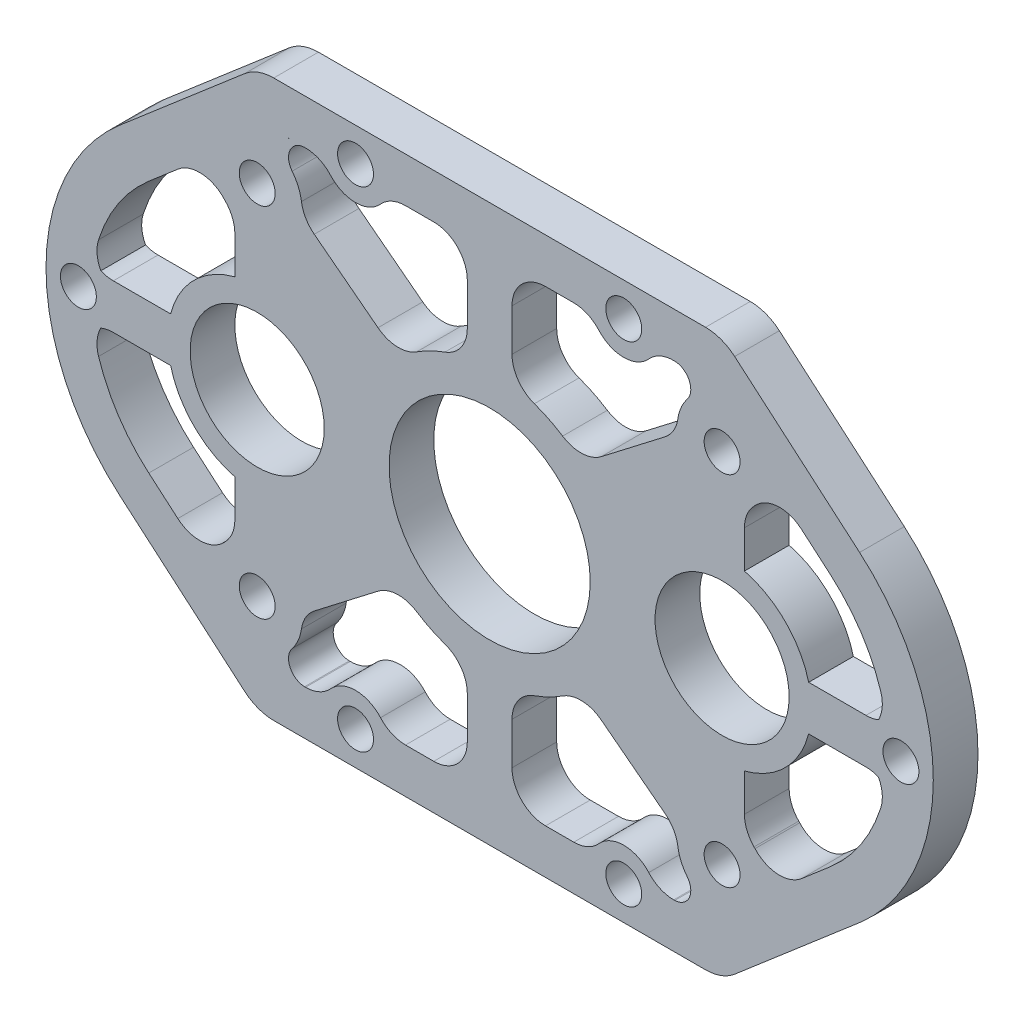
SolidWorks part; units mm, degrees
material "6061-T6 (SS)"
ref_plane "Front Plane" through (0, 0, 0) normal (0, 0, 1) x (1, 0, 0)
ref_plane "Top Plane" through (0, 0, 0) normal (0, 1, 0) x (1, 0, 0)
ref_plane "Right Plane" through (0, 0, 0) normal (1, 0, 0) x (0, 0, -1)
sketch "Sketch1" plane through (0, 0, 0) normal (0, 0, 1) x (1, 0, 0)
  line L0 (127, 25.4) -> (127, 0) construction
  line L1 (0, 0) -> (254, 0)
  line L2 (0, 0) -> (0, 25.4)
  line L3 (0, 25.4) -> (254, 25.4)
  line L4 (254, 0) -> (254, 25.4)
  line L18 (110.6338, 19.05) -> (106.9677, 12.7)
  line L19 (106.9677, 12.7) -> (110.6338, 6.35)
  line L20 (110.6338, 6.35) -> (117.9662, 6.35)
  line L21 (117.9662, 6.35) -> (121.6323, 12.7)
  line L22 (121.6323, 12.7) -> (117.9662, 19.05)
  line L23 (117.9662, 19.05) -> (110.6338, 19.05)
  circle A0 centre (81.28, 12.7) radius 30 construction
  circle A1 centre (147.32, 12.7) radius 30 construction
  circle A2 centre (81.28, 12.7) radius 7.62 construction
  circle A3 centre (147.32, 12.7) radius 8.636
  circle A4 centre (81.28, 12.7) radius 8.636
  circle A5 centre (147.32, 12.7) radius 7.62 construction
  circle A6 centre (114.3, 12.7) radius 25.4 construction
  circle A7 centre (114.3, 12.7) radius 26.67
  circle A8 centre (114.3, 12.7) radius 22.2377 construction
  circle A11 centre (114.3, 12.7) radius 6.35 construction
  point P46 (0, 12.7)
  dimension "D4" = 17.272
  dimension "D9" = 53.34
  dimension "D13" = 12.7
  dimension "D1" = 25.4
  dimension "D2" = 254
  dimension "D10" = 12.7
  dimension "D12" = 12.7
sketch "Sketch3" plane through (0, 0, 0) normal (0, 0, 1) x (1, 0, 0)
  line L0 (81.28, 42.7) -> (147.32, 42.7) construction
  line L5 (81.28, 12.7) -> (114.3, 12.7) construction
  line L6 (114.3, 12.7) -> (147.32, 12.7) construction
  line L9 (114.3, 42.7) -> (114.3, -17.3) construction
  line L10 (61.7477, 35.4704) -> (81.28, 52.225)
  line L25 (81.28, 52.225) -> (147.32, 52.225)
  line L26 (147.32, 52.225) -> (166.8523, 35.4704)
  line L27 (110.6338, 19.05) -> (106.9677, 12.7)
  line L28 (106.9677, 12.7) -> (110.6338, 6.35)
  line L29 (110.6338, 6.35) -> (117.9662, 6.35)
  line L30 (117.9662, 6.35) -> (121.6323, 12.7)
  line L31 (121.6323, 12.7) -> (117.9662, 19.05)
  line L32 (117.9662, 19.05) -> (110.6338, 19.05)
  line L33 (110.565, 18.9308) -> (106.9677, 12.7)
  line L34 (106.9677, 12.7) -> (110.6338, 6.35)
  line L35 (110.6338, 6.35) -> (117.9662, 6.35)
  line L36 (117.9662, 6.35) -> (121.6323, 12.7)
  line L37 (121.6323, 12.7) -> (117.9662, 19.05)
  line L38 (117.9662, 19.05) -> (110.6338, 19.05)
  line L39 (96.3395, 30.6605) -> (132.2605, -5.2605) construction
  line L40 (99.2405, 30.6605) -> (81.28, 12.7) construction
  line L41 (95.25, 47.4625) -> (133.35, 47.4625) construction
  line L42 (81.28, -17.3) -> (147.32, -17.3) construction
  line L43 (95.25, -22.0625) -> (133.35, -22.0625) construction
  line L44 (147.32, -26.825) -> (166.8523, -10.0704)
  line L45 (81.28, -26.825) -> (147.32, -26.825)
  line L46 (61.7477, -10.0704) -> (81.28, -26.825)
  line L47 (81.28, 12.7) -> (81.28, -12.7) construction
  line L48 (81.28, 12.7) -> (81.28, -12.7) construction
  line L49 (81.28, 12.7) -> (55.88, 12.7) construction
  circle A2 centre (81.28, 12.7) radius 30 construction
  circle A9 centre (114.3, 12.7) radius 26.67
  circle A10 centre (114.3, 12.7) radius 26.67 construction
  circle A11 centre (81.28, 12.7) radius 8.636
  circle A12 centre (81.28, 12.7) radius 8.636 construction
  circle A13 centre (147.32, 12.7) radius 8.636
  circle A16 centre (147.32, 12.7) radius 8.636 construction
  circle A17 centre (95.25, 47.4625) radius 2.5527
  circle A19 centre (114.3, 12.7) radius 25.4 construction
  circle A20 centre (114.3, 12.7) radius 22.2377 construction
  circle A22 centre (114.3, 12.7) radius 25.4 construction
  circle A23 centre (114.3, 12.7) radius 22.2377 construction
  arc A24 (108.3271, 25.6791) -> (108.3271, -0.2791) centre (81.28, 12.7) ccw
  circle A25 centre (114.3, 12.7) radius 14.2875
  circle A26 centre (81.28, 12.7) radius 9.525
  circle A27 centre (147.32, 12.7) radius 9.525
  circle A37 centre (133.35, 47.4625) radius 2.5527
  circle A38 centre (133.35, -22.0625) radius 2.5527
  circle A39 centre (95.25, -22.0625) radius 2.5527
  circle A40 centre (81.28, -12.7) radius 2.5527
  circle A41 centre (55.88, 12.7) radius 2.5527
  circle A42 centre (81.28, 38.1) radius 2.5527
  circle A43 centre (147.32, -12.7) radius 2.5527
  circle A44 centre (172.72, 12.7) radius 2.5527
  circle A45 centre (147.32, 38.1) radius 2.5527
  arc A47 (120.2729, -0.2791) -> (120.2729, 25.6791) centre (147.32, 12.7) ccw
  point P2 (114.3, 42.7)
  point P41 (114.3, 52.225)
  point P59 (114.3, 47.4625)
  point P69 (114.3, 12.7)
  point P78 (81.28, 12.7)
  point P84 (114.3, -22.0625)
  dimension "D3" = 45
  dimension "D4" = 9.525
  dimension "D2" = 45
  dimension "D8" = 25.4
  dimension "D14" = 28.575
  dimension "D15" = 19.05
  dimension "D16" = 3
  dimension "D5" = 5.1054
  dimension "D12" = 5.1054
  dimension "D7" = 4.7625
  dimension "D17" = 90
  dimension "2" = 50.8
  dimension "D6" = 19.05
  dimension "D9" = 0
  dimension "D10" = 0
  dimension "D11" = 0
  dimension "D13" = 0
extrude "Boss-Extrude1" add sketch "Sketch3" along normal blind 6.35 contours A24 A10 L26 L25 L10 A37 A17 | A24 L46 L45 L44 A10 A38 A39 | A10 A24 A12 A40 A42 | A23 A24 A25 | A23 A22 A12 | A22 A24 A10 A12 | A22 A12 A10 A24 | A24 A22 A23 | A24 A10 A22 | A22 A24 A23 | A25 A24 A23 | A25 A23 A24 | A24 A23 A22 | A24 A22 A10 | A23 A24 A22 | A23 A45 A25 A44 | A22 A45 A23 A44 A16 | A23 A45 A22 | A22 A45 A16 A10 | A10 A16 A43 | A22 A44 A23 | A22 A44 A10 A16 | A10 A26 A12 | A22 A12 A10 | A12 A22 | A10 A27 A16 | A16 A22 | A22 A16 A10 region at (81.1746, 41.9228, 0) region at (114.3, 45.5045, 0) region at (114.3, -20.1045, 0) region at (97.63, 12.7, 0) region at (114.3, 33.2042, 0) region at (114.3, -7.8042, 0) region at (147.4254, 41.9228, 0) region at (130.97, 12.7, 0)
fillet "Fillet2" radius 6.35 4 edges at (147.32, -26.825, 3.175) (81.28, -26.825, 3.175) (147.32, 52.225, 3.175) (81.28, 52.225, 3.175)
sketch "Sketch9" plane through (0, 0, 6.35) normal (0, 0, 1) x (1, 0, 0)
  line L0 (144.9696, -20.475) -> (162.7179, -5.2507)
  line L1 (162.7179, 30.6507) -> (144.9696, 45.875)
  line L2 (144.9696, 45.875) -> (83.6304, 45.875)
  line L3 (83.6304, 45.875) -> (65.8821, 30.6507)
  line L4 (65.8821, -5.2507) -> (83.6304, -20.475)
  line L5 (83.6304, -20.475) -> (144.9696, -20.475)
  line L6 (149.104, -25.2947) -> (166.8523, -10.0704)
  line L7 (166.8523, 35.4704) -> (149.104, 50.6947)
  line L8 (144.9696, 52.225) -> (83.6304, 52.225)
  line L9 (79.496, 50.6947) -> (61.7477, 35.4704)
  line L10 (61.7477, -10.0704) -> (79.496, -25.2947)
  line L11 (83.6304, -26.825) -> (144.9696, -26.825)
  line L12 (149.104, -25.2947) -> (166.8523, -10.0704)
  line L13 (166.8523, 35.4704) -> (149.104, 50.6947)
  line L14 (144.9696, 52.225) -> (83.6304, 52.225)
  line L15 (79.496, 50.6947) -> (61.7477, 35.4704)
  line L16 (61.7477, -10.0704) -> (79.496, -25.2947)
  line L17 (83.6304, -26.825) -> (144.9696, -26.825)
  line L18 (81.28, 38.1) -> (81.28, 12.7) construction
  line L19 (81.28, 12.7) -> (81.28, -12.7) construction
  line L20 (147.32, -12.7) -> (147.32, 12.7) construction
  line L21 (147.32, 12.7) -> (147.32, 38.1) construction
  line L22 (81.28, 12.7) -> (114.3, 12.7) construction
  line L23 (114.3, 12.7) -> (147.32, 12.7) construction
  line L24 (147.32, 12.7) -> (114.3, 12.7) construction
  line L25 (114.3, 12.7) -> (147.32, -12.7) construction
  line L26 (81.28, -12.7) -> (114.3, 12.7) construction
  line L27 (114.3, 12.7) -> (81.28, 38.1) construction
  line L28 (114.3, 12.7) -> (147.32, 38.1) construction
  line L29 (114.3, 12.7) -> (114.3, 45.875) construction
  line L30 (114.3, 12.7) -> (114.3, -20.475) construction
  line L31 (116.2358, 15.2166) -> (83.2158, 40.6166)
  line L32 (112.3642, 10.1834) -> (145.3842, -15.2166)
  line L33 (116.2358, 10.1834) -> (149.2558, 35.5834)
  line L34 (112.3642, 10.1834) -> (79.3442, 35.5834)
  line L35 (116.2358, 15.2166) -> (149.2558, -10.1834)
  line L36 (112.3642, 15.2166) -> (145.3842, 40.6166)
  line L37 (81.28, 12.7) -> (55.88, 12.7) construction
  line L38 (147.32, 12.7) -> (172.72, 12.7) construction
  line L39 (81.28, 9.525) -> (55.88, 9.525)
  line L40 (81.28, 9.525) -> (114.3, 9.525)
  line L41 (114.3, 9.525) -> (147.32, 9.525)
  line L42 (147.32, 9.525) -> (172.72, 9.525)
  line L43 (81.28, 15.875) -> (55.88, 15.875)
  line L44 (81.28, 15.875) -> (114.3, 15.875)
  line L45 (114.3, 15.875) -> (147.32, 15.875)
  line L46 (147.32, 15.875) -> (172.72, 15.875)
  line L47 (83.2158, -15.2166) -> (116.2358, 10.1834)
  line L48 (79.3442, -10.1834) -> (112.3642, 15.2166)
  line L49 (111.125, 12.7) -> (111.125, -20.475)
  line L50 (117.475, 12.7) -> (117.475, -20.475)
  line L51 (117.475, 12.7) -> (117.475, 45.875)
  line L52 (111.125, 12.7) -> (111.125, 45.875)
  line L53 (78.105, 38.1) -> (78.105, 12.7)
  line L54 (78.105, 12.7) -> (78.105, -12.7)
  line L55 (150.495, -12.7) -> (150.495, 12.7)
  line L56 (150.495, 12.7) -> (150.495, 38.1)
  line L57 (84.455, 38.1) -> (84.455, 12.7)
  line L58 (84.455, 12.7) -> (84.455, -12.7)
  line L59 (144.145, -12.7) -> (144.145, 12.7)
  line L60 (144.145, 12.7) -> (144.145, 38.1)
  circle A0 centre (55.88, 12.7) radius 4.6
  circle A1 centre (95.25, 47.4625) radius 4.7625
  arc A2 (166.8523, -10.0704) -> (166.8523, 35.4704) centre (147.32, 12.7) ccw
  arc A3 (61.7477, 35.4704) -> (61.7477, -10.0704) centre (81.28, 12.7) ccw
  arc A4 (166.8523, -10.0704) -> (166.8523, 35.4704) centre (147.32, 12.7) ccw
  arc A5 (61.7477, 35.4704) -> (61.7477, -10.0704) centre (81.28, 12.7) ccw
  circle A6 centre (133.35, 47.4625) radius 4.7625
  circle A7 centre (172.72, 12.7) radius 4.6
  circle A8 centre (133.35, -22.0625) radius 4.7625
  circle A9 centre (95.25, -22.0625) radius 4.7625
  circle A10 centre (81.28, 12.7) radius 9.525
  circle A11 centre (81.28, -12.7) radius 6.35
  circle A12 centre (81.28, 38.1) radius 6.35
  circle A13 centre (147.32, 38.1) radius 6.35
  circle A14 centre (147.32, 12.7) radius 9.525
  circle A15 centre (147.32, -12.7) radius 6.35
  arc A16 (144.9696, -26.825) -> (149.104, -25.2947) centre (144.9696, -20.475) ccw
  arc A17 (144.9696, -26.825) -> (149.104, -25.2947) centre (144.9696, -20.475) ccw
  arc A18 (149.104, 50.6947) -> (144.9696, 52.225) centre (144.9696, 45.875) ccw
  arc A19 (149.104, 50.6947) -> (144.9696, 52.225) centre (144.9696, 45.875) ccw
  arc A20 (83.6304, 52.225) -> (79.496, 50.6947) centre (83.6304, 45.875) ccw
  arc A21 (83.6304, 52.225) -> (79.496, 50.6947) centre (83.6304, 45.875) ccw
  arc A22 (79.496, -25.2947) -> (83.6304, -26.825) centre (83.6304, -20.475) ccw
  arc A23 (79.496, -25.2947) -> (83.6304, -26.825) centre (83.6304, -20.475) ccw
  arc A24 (162.7179, -5.2507) -> (162.7179, 30.6507) centre (147.32, 12.7) ccw
  arc A25 (144.9696, 45.875) -> (144.9696, 45.875) centre (144.9696, 45.875) ccw
  arc A26 (83.6304, 45.875) -> (83.6304, 45.875) centre (83.6304, 45.875) ccw
  arc A27 (65.8821, 30.6507) -> (65.8821, -5.2507) centre (81.28, 12.7) ccw
  arc A28 (83.6304, -20.475) -> (83.6304, -20.475) centre (83.6304, -20.475) ccw
  arc A29 (144.9696, -20.475) -> (144.9696, -20.475) centre (144.9696, -20.475) ccw
  circle A30 centre (114.3, 12.7) radius 19.05
  circle A32 centre (81.28, 12.7) radius 12.7
  circle A33 centre (147.32, 12.7) radius 12.7
  dimension "D2" = 19.05
  dimension "D3" = 12.7
  dimension "D4" = 38.1
  dimension "D18" = 25.4
  dimension "D17" = 6.35
  dimension "D1" = 0
  dimension "D5" = 3.175
  dimension "D6" = 3.175
  dimension "D7" = 3.175
  dimension "D8" = 3.175
  dimension "D9" = 3.175
  dimension "D10" = 3.175
  dimension "D11" = 3.175
  dimension "D12" = 3.175
  dimension "D13" = 3.175
  dimension "D14" = 3.175
  dimension "D15" = 3.175
  dimension "D16" = 3.175
extrude "Cut-Extrude2" cut sketch "Sketch9" against normal blind 6.35 contours A32 L53 A12 L3 A27 A0 L43 | A32 L39 A0 A27 L4 A11 L54 | A30 L52 L2 A1 L3 A12 L31 | A30 L36 A13 L1 L2 A6 L51 | A33 L46 A7 A24 L1 A13 L56 | A33 L55 A15 L0 A24 A7 L42 | A30 L50 L5 A8 L0 A15 L32 | A30 L47 A11 L4 L5 A9 L49 region at (128.7733, -12.6609, 6.35) region at (159.8487, -0.042, 6.35) region at (99.8267, -12.6609, 6.35) region at (159.8487, 25.442, 6.35) region at (68.7513, -0.042, 6.35) region at (128.7733, 38.0609, 6.35) region at (68.7513, 25.442, 6.35) region at (99.8267, 38.0609, 6.35)
fillet "Fillet3" radius 4.7625 48 edges at (117.475, 45.875, 3.175) (128.8599, 45.875, 3.175) (137.8401, 45.875, 3.175) (144.9696, 45.875, 3.175) (146.6698, 44.4166, 3.175) (141.0253, 37.2636, 3.175) (127.2525, 26.6691, 3.175) (117.475, 31.4836, 3.175) (101.3475, 26.6691, 3.175) (81.9302, 44.4166, 3.175) (83.6304, 45.875, 3.175) (90.7599, 45.875, 3.175) (99.7401, 45.875, 3.175) (111.125, 45.875, 3.175) (111.125, 31.4836, 3.175) (87.5747, 37.2636, 3.175) (111.125, -6.0836, 3.175) (111.125, -20.475, 3.175) (99.7401, -20.475, 3.175) (90.7599, -20.475, 3.175) (81.9302, -19.0166, 3.175) (87.5747, -11.8636, 3.175) (101.3475, -1.2691, 3.175) (83.6304, -20.475, 3.175) (127.2525, -1.2691, 3.175) (141.0253, -11.8636, 3.175) (146.6698, -19.0166, 3.175) (144.9696, -20.475, 3.175) (137.8401, -20.475, 3.175) (128.8599, -20.475, 3.175) (117.475, -6.0836, 3.175) (117.475, -20.475, 3.175) (169.3914, 15.875, 3.175) (150.495, 32.6007, 3.175) (153.662, 38.4188, 3.175) (170.6137, 16.7895, 3.175) (78.105, 32.6007, 3.175) (59.2086, 15.875, 3.175) (74.938, 38.4188, 3.175) (57.9863, 16.7895, 3.175) (78.105, -7.2007, 3.175) (74.938, -13.0188, 3.175) (57.9863, 8.6105, 3.175) (59.2086, 9.525, 3.175) (150.495, -7.2007, 3.175) (153.662, -13.0188, 3.175) (169.3914, 9.525, 3.175) (170.6137, 8.6105, 3.175)
sketch "Sketch11" plane through (0, 0, 6.35) normal (0, 0, 1) x (1, 0, 0)
  line L4 (53.3273, 12.7) -> (175.2727, 12.7) construction
  line L5 (114.3, 52.225) -> (114.3, -26.825) construction
  line L6 (83.6304, 52.225) -> (144.9696, 52.225) construction
  line L7 (83.6304, -26.825) -> (144.9696, -26.825) construction
  line L16 (143.3237, -20.4736) -> (140.4495, -20.475)
  line L17 (143.3237, 45.8736) -> (140.4495, 45.875)
  line L18 (85.2763, 45.8736) -> (88.1505, 45.875)
  line L19 (85.3931, -20.475) -> (88.1505, -20.475) construction
  line L20 (85.3931, -20.475) -> (88.1505, -20.475)
  circle A1 centre (55.88, 12.7) radius 2.5527 construction
  circle A3 centre (172.72, 12.7) radius 2.5527 construction
  arc A17 (86.2424, -16.662) -> (88.1505, -20.475) centre (88.0778, -18.1274) ccw
  arc A18 (86.2424, -16.662) -> (87.568, -13.5855) centre (81.28, -12.7) ccw construction
  arc A19 (86.2424, -16.662) -> (85.2763, -20.4736) centre (89.9642, -19.6335) ccw construction
  arc A21 (142.3576, -16.662) -> (143.3237, -20.4736) centre (138.6358, -19.6335) cw
  arc A22 (142.3576, -16.662) -> (140.4495, -20.475) centre (140.5222, -18.1274) cw
  arc A23 (142.3576, 42.062) -> (140.4495, 45.875) centre (140.5222, 43.5274) ccw
  arc A24 (142.3576, 42.062) -> (143.3237, 45.8736) centre (138.6358, 45.0335) ccw
  arc A25 (86.2424, 42.062) -> (85.2763, 45.8736) centre (89.9642, 45.0335) cw
  arc A26 (86.2424, 42.062) -> (88.1505, 45.875) centre (88.0778, 43.5274) cw
  arc A27 (85.2763, -20.4736) -> (85.3931, -20.475) centre (85.3931, -15.7125) ccw construction
  arc A28 (85.2763, -20.4736) -> (85.3931, -20.475) centre (85.3931, -15.7125) ccw
  arc A29 (86.2424, -16.662) -> (85.2763, -20.4736) centre (89.9642, -19.6335) ccw
extrude "Boss-Extrude3" add sketch "Sketch11" against normal up to surface (6.35 mm away) contours A17 A29 A28 L20 | A21 A22 L16 | A25 A26 L18 | A23 A24 L17 | L17 A23 A24 region at (142.7262, -19.5499, 6.35) region at (142.7262, 44.9499, 6.35) region at (85.8738, 44.9499, 6.35) region at (85.8741, -19.5506, 6.35) up to face at (96.993, 39.8725, 0)
equation "\"NEO\"= 60mm"
equation "\"D3@Sketch1\"=\"NEO\""
equation "\"D5@Sketch1\"=\"NEO\""
